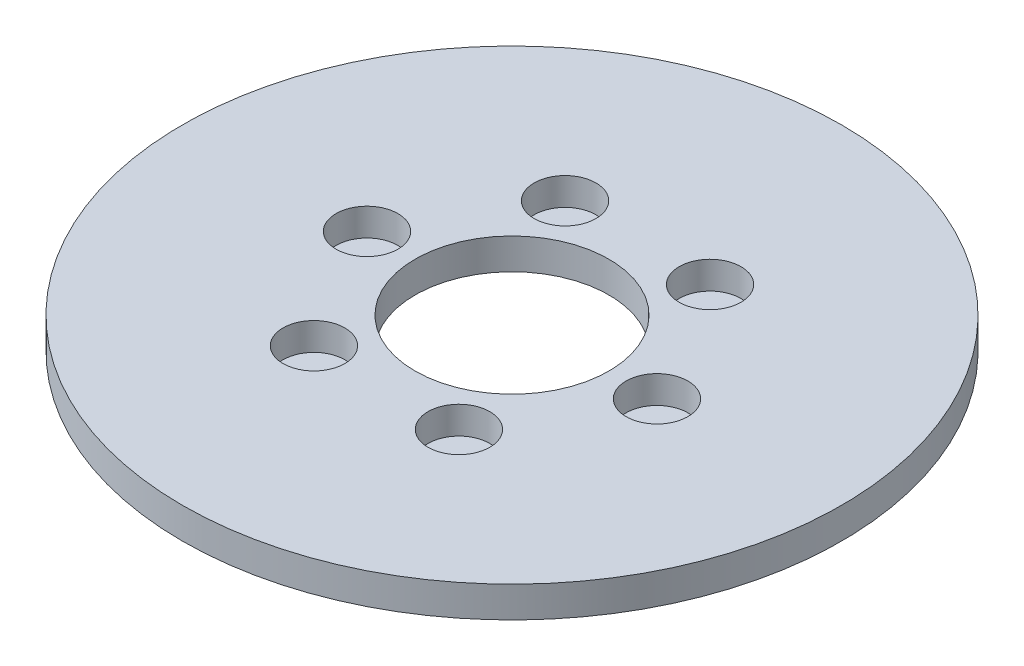
SolidWorks part; units mm, degrees
ref_plane "Front Plane" through (0, 0, 0) normal (0, 0, 1) x (1, 0, 0)
ref_plane "Top Plane" through (0, 0, 0) normal (0, 1, 0) x (1, 0, 0)
ref_plane "Right Plane" through (0, 0, 0) normal (1, 0, 0) x (0, 0, -1)
sketch "Sketch1" plane through (0, 0, 0) normal (0, 1, 0) x (1, 0, 0)
  circle A0 centre (0, 0) radius 85
  dimension "FLANGE_OD" = 170
extrude "Boss-Extrude1" add sketch "Sketch1" along normal blind 8
sketch "Sketch2" plane through (0, 0, 0) normal (0, 1, 0) x (1, 0, 0)
  circle A0 centre (0, 0) radius 25
  dimension "BORE_D" = 50
extrude "Cut-Extrude1" cut sketch "Sketch2" along normal through all
sketch "Sketch3" plane through (0, 8, 0) normal (0, 1, 0) x (1, 0, 0)
  circle A0 centre (0, 0) radius 37.3953 construction
  circle A1 centre (-37.3953, 0) radius 7.9692
  dimension "BOLT_D" = 15.9383
  dimension "BOLT_PCD" = 74.7906
extrude "Cut-Extrude2" cut sketch "Sketch3" against normal blind 7.1178
pattern_circular "CirPattern1" count 6 over 360 about axis through (0, 0, 0) along (0, 1, 0) of "Cut-Extrude2"
